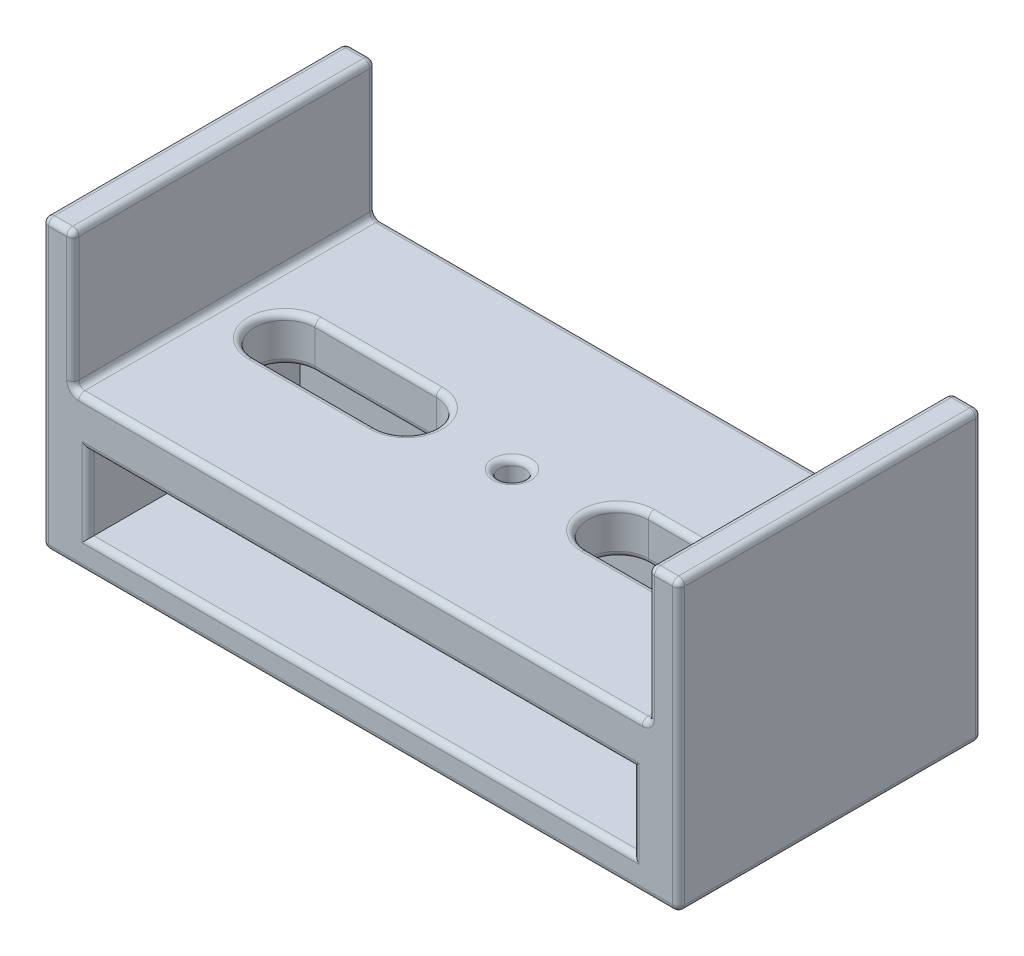
SolidWorks part; units mm, degrees
ref_plane "前视基准面" through (0, 0, 0) normal (0, 0, 1) x (1, 0, 0)
ref_plane "上视基准面" through (0, 0, 0) normal (0, 1, 0) x (1, 0, 0)
ref_plane "右视基准面" through (0, 0, 0) normal (1, 0, 0) x (0, 0, -1)
other "Configuration Table"
sketch "草图1" plane through (0, 0, 0) normal (0, 1, 0) x (1, 0, 0)
  line L1 (0, 0) -> (210, 0)
  line L2 (0, 0) -> (0, -100)
  line L3 (0, -100) -> (210, -100)
  line L4 (210, 0) -> (210, -100)
  dimension "D1" = 210
  dimension "D2" = 100
extrude "凸台-拉伸1" add sketch "草图1" along normal blind 50
sketch "草图2" plane through (0, 50, 0) normal (0, 1, 0) x (1, 0, 0)
  line L0 (0, -50) -> (210, -50) construction
  line L1 (0, 0) -> (0, -100) construction
  line L2 (210, -100) -> (210, 0) construction
  line L3 (105, 0) -> (105, -100) construction
  line L4 (210, 0) -> (0, 0) construction
  line L5 (0, -100) -> (210, -100) construction
  line L6 (30, -50) -> (70, -50) construction
  line L7 (30, -40) -> (70, -40)
  line L8 (30, -60) -> (70, -60)
  line L9 (140, -50) -> (180, -50) construction
  line L10 (140, -40) -> (180, -40)
  line L11 (140, -60) -> (180, -60)
  arc A0 (30, -40) -> (30, -60) centre (30, -50) ccw
  arc A1 (70, -60) -> (70, -40) centre (70, -50) ccw
  arc A2 (140, -40) -> (140, -60) centre (140, -50) ccw
  arc A3 (180, -60) -> (180, -40) centre (180, -50) ccw
  point P12 (105, -50)
  point P15 (50, -50)
  point P20 (160, -50)
  dimension "D3" = 10
  dimension "D1" = 35
  dimension "D2" = 40
  dimension "D4" = 35
extrude "切除-拉伸1" cut sketch "草图2" against normal blind 40
sketch "草图3" plane through (0, 0, 100) normal (0, 0, 1) x (1, 0, 0)
  line L0 (210, 50) -> (210, 0) construction
  line L1 (15, 10) -> (195, 10)
  line L2 (15, 10) -> (15, 35)
  line L3 (15, 35) -> (195, 35)
  line L4 (195, 10) -> (195, 35)
  line L5 (0, 50) -> (0, 0) construction
  line L6 (0, 0) -> (210, 0) construction
  dimension "D1" = 15
  dimension "D2" = 15
  dimension "D3" = 25
  dimension "D4" = 10
extrude "切除-拉伸2" cut sketch "草图3" against normal blind 70
sketch "草图4" plane through (0, 50, 0) normal (0, 1, 0) x (1, 0, 0)
  circle A0 centre (105, -50) radius 4.25
  dimension "D1" = 8.5
extrude "切除-拉伸3" cut sketch "草图4" against normal blind 20
fillet "圆角4" radius 2 18 edges at (190, 50, 50) (160, 50, 60) (130, 50, 50) (130, 35, 50) (160, 35, 60) (190, 35, 50) (80, 50, 50) (50, 50, 60) (20, 50, 50) (20, 35, 50) (50, 35, 60) (80, 35, 50) (160, 50, 40) (160, 35, 40) (50, 50, 40) (50, 35, 40) (105, 35, 54.25) (105, 50, 54.25)
sketch "草图6" plane through (0, 50, 0) normal (0, 1, 0) x (1, 0, 0)
  line L0 (105, 0) -> (105, -100) construction
  line L1 (210, 0) -> (0, 0) construction
  line L2 (0, -100) -> (210, -100) construction
  line L3 (210, -100) -> (200, -100)
  line L4 (0, 0) -> (10, 0)
  line L5 (0, 0) -> (0, -100)
  line L6 (0, -100) -> (10, -100)
  line L7 (10, 0) -> (10, -100)
  line L8 (210, 0) -> (210, -100)
  line L9 (210, 0) -> (200, 0)
  line L10 (200, 0) -> (200, -100)
  circle A0 centre (105, -50) radius 100 construction
  dimension "D1" = 200
  dimension "D2" = 95
extrude "凸台-拉伸2" add sketch "草图6" along normal blind 45
fillet "圆角7" radius 2 28 edges at (0, 95, 50) (0, 0, 50) (210, 95, 50) (210, 0, 50) (200, 95, 50) (200, 50, 50) (10, 95, 50) (10, 50, 50) (210, 47.5, 0) (205, 95, 0) (200, 72.5, 0) (105, 50, 0) (10, 72.5, 0) (5, 95, 0) (0, 47.5, 0) (105, 0, 0) (0, 47.5, 100) (5, 95, 100) (10, 72.5, 100) (105, 50, 100) (200, 72.5, 100) (205, 95, 100) (210, 47.5, 100) (105, 0, 100) (195, 22.5, 100) (105, 35, 100) (15, 22.5, 100) (105, 10, 100)
